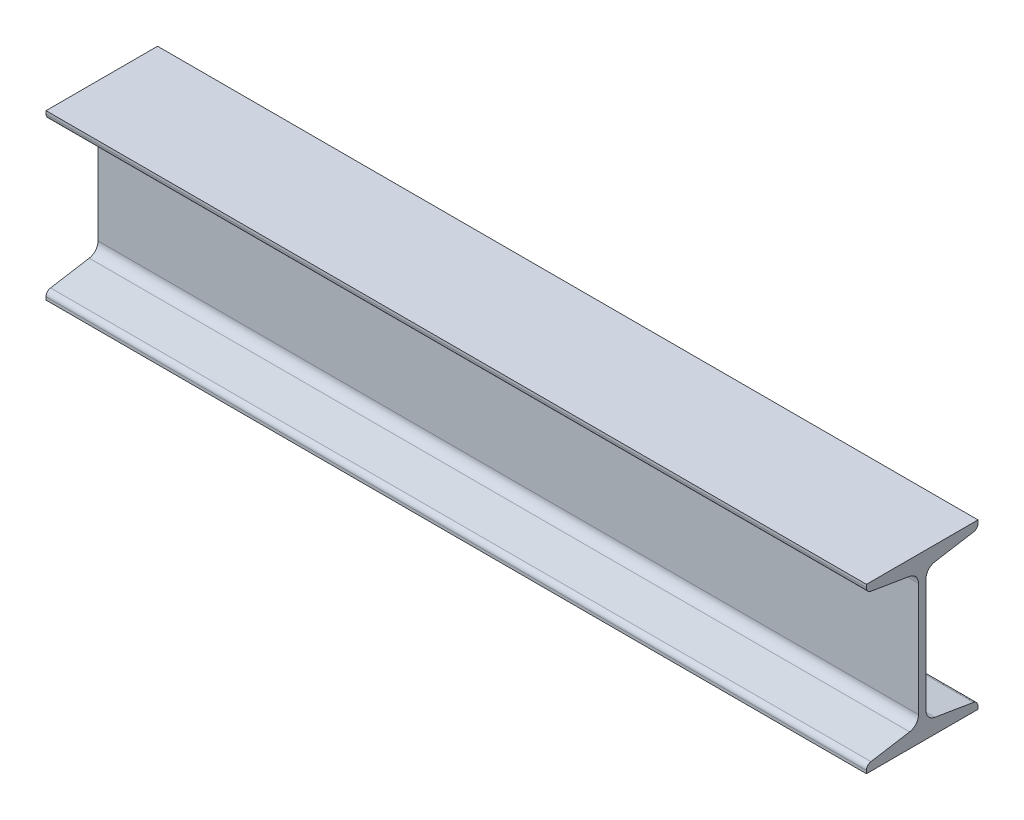
SolidWorks part; units mm, degrees
ref_plane "Front" through (0, 0, 0) normal (0, 0, 1) x (1, 0, 0)
ref_plane "Top" through (0, 0, 0) normal (0, 1, 0) x (1, 0, 0)
ref_plane "Right" through (0, 0, 0) normal (1, 0, 0) x (0, 0, -1)
sketch "Sketch1" plane through (0, 0, 0) normal (1, 0, 0) x (0, 0, -1)
  line L0 (-34, 0) -> (34, 0)
  line L1 (0, 106.3348) -> (0, -35.2641) construction
  line L2 (-2.25, 90.1292) -> (-2.25, 9.8708)
  line L3 (-2.25, 9.8708) -> (-34, 4.5792)
  line L4 (-34, 4.5792) -> (-34, 0)
  line L5 (-34, 4.5792) -> (-2.25, 4.5792) construction
  line L6 (-2.25, 4.5792) -> (-2.25, 9.8708) construction
  line L7 (-15.875, 100) -> (-15.875, 0) construction
  line L8 (-34, 100) -> (34, 100)
  line L9 (-34, 100) -> (-34, 95.4208)
  line L10 (-34, 95.4208) -> (-2.25, 90.1292)
  line L11 (-34, 95.4208) -> (-2.25, 95.4208) construction
  line L12 (-2.25, 95.4208) -> (-2.25, 90.1292) construction
  line L13 (-15.875, 7.6) -> (-15.875, 0) construction
  line L14 (-15.875, 100) -> (-15.875, 92.4) construction
  line L15 (34, 4.5792) -> (34, 0)
  line L16 (2.25, 9.8708) -> (34, 4.5792)
  line L17 (2.25, 90.1292) -> (2.25, 9.8708)
  line L18 (34, 95.4208) -> (2.25, 90.1292)
  line L19 (34, 100) -> (34, 95.4208)
  point P22 (0, 100)
  dimension "D5" = 5.2917
  dimension "D6" = 15.875
  dimension "D10" = 5.2917
extrude "Base" add sketch "Sketch1" along normal blind 500
fillet "Fillet1" radius 6.5 4 edges at (250, 90.1292, -2.25) (250, 9.8708, -2.25) (250, 9.8708, 2.25) (250, 90.1292, 2.25)
fillet "Fillet2" radius 3.3 4 edges at (250, 95.4208, 34) (250, 4.5792, 34) (250, 4.5792, -34) (250, 95.4208, -34)
equation "\"D5@Sketch1\" =  ( \"b@Sketch1\" - \"d@Sketch1\" ) /12"
equation "\"D10@Sketch1\" = \"D5@Sketch1\""
equation "\"t1@Sketch1\" = \"t@Sketch1\""
equation "\"D6@Sketch1\" =  ( \"b@Sketch1\" - \"d@Sketch1\" ) /4"
